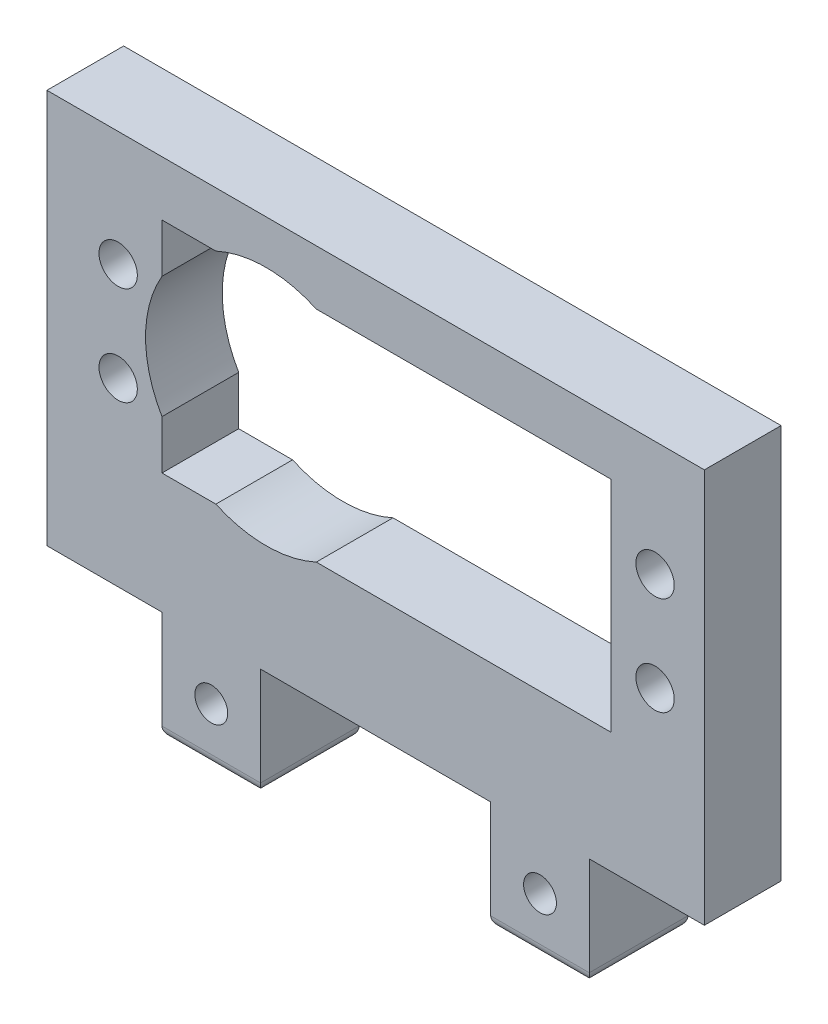
SolidWorks part; units mm, degrees
ref_plane "Alzado" through (0, 0, 0) normal (0, 0, 1) x (1, 0, 0)
ref_plane "Planta" through (0, 0, 0) normal (0, 1, 0) x (1, 0, 0)
ref_plane "Vista lateral" through (0, 0, 0) normal (1, 0, 0) x (0, 0, -1)
sketch "Croquis1" plane through (0, 0, 0) normal (0, 0, 1) x (1, 0, 0)
  line L0 (10.5, -10) -> (49.5, -10) construction
  line L1 (0, 0) -> (60, 0)
  line L2 (0, 0) -> (0, 36)
  line L3 (0, 36) -> (60, 36)
  line L4 (60, 0) -> (60, 36)
  line L5 (10.5, -5) -> (49.5, -5) construction
  line L6 (10.5, -10) -> (19.5, -10)
  line L7 (10.5, -10) -> (10.5, 0)
  line L8 (10.5, 0) -> (19.5, 0)
  line L9 (19.5, -10) -> (19.5, 0)
  line L10 (49.5, -10) -> (40.5, -10)
  line L11 (49.5, -10) -> (49.5, 0)
  line L12 (49.5, 0) -> (40.5, 0)
  line L13 (40.5, -10) -> (40.5, 0)
  line L14 (10.5, 31) -> (51.5, 31)
  line L15 (10.5, 31) -> (10.5, 11)
  line L16 (10.5, 11) -> (51.5, 11)
  line L17 (51.5, 31) -> (51.5, 11)
  line L18 (15, -10) -> (15, 0) construction
  line L19 (45, -10) -> (45, 0) construction
  line L20 (55.5, 35.4132) -> (55.5, -2.9176) construction
  line L21 (6.5, 40.3733) -> (6.5, 2.0424) construction
  line L22 (6.5, 21) -> (55.5, 21) construction
  line L23 (6.5, 25.5) -> (55.5, 25.5) construction
  line L24 (6.5, 16.5) -> (55.5, 16.5) construction
  circle A0 centre (6.5, 25.5) radius 1.75
  circle A1 centre (6.5, 16.5) radius 1.75
  circle A2 centre (55.5, 25.5) radius 1.75
  circle A3 centre (55.5, 16.5) radius 1.75
  circle A4 centre (15, -5) radius 1.5
  circle A5 centre (45, -5) radius 1.5
  circle A6 centre (20, 21) radius 11
  point P37 (20, 21)
  dimension "D14" = 3.5
  dimension "D15" = 3.5
  dimension "D16" = 3.5
  dimension "D17" = 3.5
  dimension "D21" = 3
  dimension "D22" = 3
  dimension "D23" = 22
  dimension "D1" = 10
  dimension "D2" = 10.5
  dimension "D3" = 9
  dimension "D4" = 10.5
  dimension "D5" = 9
  dimension "D6" = 60
  dimension "D7" = 41
  dimension "D8" = 4
  dimension "D9" = 4
  dimension "D10" = 20
  dimension "D11" = 10
  dimension "D12" = 4.5
  dimension "D13" = 4.5
  dimension "D18" = 9.5
  dimension "D19" = 21
  dimension "D20" = 5
  dimension "D24" = 20
extrude "Saliente-Extruir1" add sketch "Croquis1" along normal blind 9 contours L1 L4 L3 L2 A6 L14 L17 L16 L15 A3 A2 A1 A0 | L6 L9 L1 L7 A4 | L13 L10 L11 L1 A5 region at (0.6997, 18, 0) region at (15, -0.1345, 0) region at (45, -0.1345, 0)
fillet "Redondeo1" radius 1 8 edges at (40.5, -10, 4.5) (45, -10, 9) (49.5, -10, 4.5) (45, -10, 0) (10.5, -10, 4.5) (15, -10, 9) (19.5, -10, 4.5) (15, -10, 0)
sketch "Croquis2" plane through (0, 0, 0) normal (-1, 0, 0) x (0, 0, 1)
  line L0 (9, 0) -> (0, 0) construction
  line L1 (9, 36) -> (4.5, 36)
  line L2 (9, 36) -> (9, 0)
  line L3 (9, 0) -> (4.5, 0)
  line L4 (4.5, 36) -> (4.5, 0)
  line L5 (2, 36) -> (2, 0)
  line L6 (4.5, 36) -> (0, 36)
  line L7 (4.5, 36) -> (4.5, 0)
  line L8 (4.5, 0) -> (0, 0)
  line L9 (0, 36) -> (0, 0)
  line M5 (0, 36) -> (0, 0)
  line M6 (0, 0) -> (9, 0)
  line M8 (9, 36) -> (0, 36)
  dimension "D1" = 7
extrude "Cortar-Extruir1" cut sketch "Croquis2" against normal through all contours L5 M8 M5 M6 region at (0, 18, 1)
fillet "Redondeo2" radius 3 2 edges at (45, 0, 2) (15, 0, 2)
